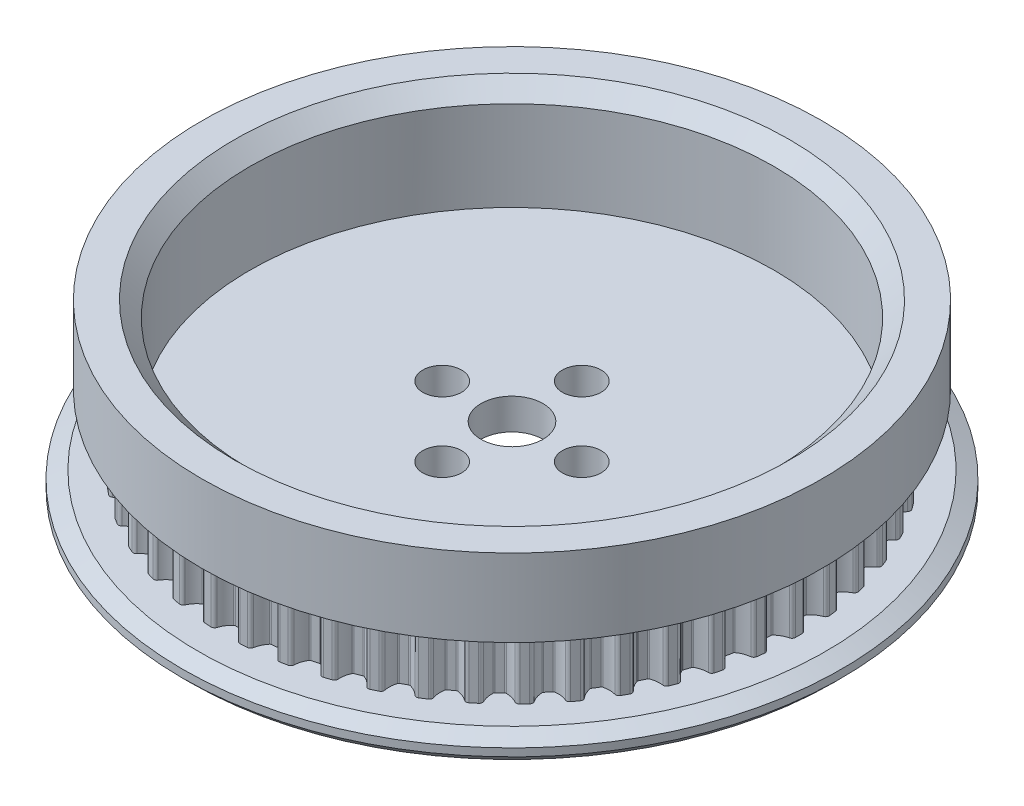
SolidWorks part; units mm, degrees
material "Markforged"
ref_plane "Front Plane" through (0, 0, 0) normal (0, 0, 1) x (1, 0, 0)
ref_plane "Top Plane" through (0, 0, 0) normal (0, 1, 0) x (1, 0, 0)
ref_plane "Right Plane" through (0, 0, 0) normal (1, 0, 0) x (0, 0, -1)
sketch "Sketch1" plane through (0, 0, 0) normal (0, 1, 0) x (1, 0, 0)
  line L0 (0, 0) -> (0, 22.38) construction
  arc B0 (21.7341, -8.9112) -> (21.9436, -8.382) centre (0, 0) ccw
  arc B1 (21.9436, -8.382) -> (21.8443, -8.0539) centre (21.682, -8.2821) ccw
  arc B2 (21.2042, -7.2904) -> (21.8443, -8.0539) centre (22.9888, -6.4443) ccw
  arc B3 (21.1977, -7.178) -> (21.2042, -7.2904) centre (21.3397, -7.2261) ccw
  arc B4 (21.1977, -7.178) -> (21.3684, -6.6526) centre (0, 0) ccw
  arc B5 (21.4397, -6.5655) -> (21.3684, -6.6526) centre (21.5116, -6.6971) ccw
  arc B6 (22.4064, -6.324) -> (21.4397, -6.5655) centre (22.3862, -8.2989) ccw
  arc B7 (22.4064, -6.324) -> (22.6796, -6.1169) centre (22.4092, -6.044) ccw
  arc B8 (22.6796, -6.1169) -> (22.8211, -5.5657) centre (0, 0) ccw
  arc B9 (22.8211, -5.5657) -> (22.6815, -5.2526) centre (22.5491, -5.4993) ccw
  arc B10 (21.9507, -4.5753) -> (22.6815, -5.2526) centre (23.6152, -3.5123) ccw
  arc B11 (21.9302, -4.4646) -> (21.9507, -4.5753) centre (22.0771, -4.4945) ccw
  arc B12 (21.9302, -4.4646) -> (22.0337, -3.9219) centre (0, 0) ccw
  arc B13 (22.0935, -3.8266) -> (22.0337, -3.9219) centre (22.1814, -3.9482) ccw
  arc B14 (23.0223, -3.4659) -> (22.0935, -3.8266) centre (23.2498, -5.4277) ccw
  arc B15 (23.0223, -3.4659) -> (23.2674, -3.2262) centre (22.99, -3.1877) ccw
  arc B16 (23.2674, -3.2262) -> (23.3387, -2.6615) centre (0, 0) ccw
  arc B17 (23.3387, -2.6615) -> (23.1609, -2.3684) centre (23.0605, -2.6298) ccw
  arc B18 (22.3511, -1.788) -> (23.1609, -2.3684) centre (23.8692, -0.5248) ccw
  arc B19 (22.3168, -1.6808) -> (22.3511, -1.788) centre (22.4664, -1.6921) ccw
  arc B20 (22.3168, -1.6808) -> (22.3515, -1.1295) centre (0, 0) ccw
  arc B21 (22.3989, -1.0274) -> (22.3515, -1.1295) centre (22.5013, -1.137) ccw
  arc B22 (23.2752, -0.5531) -> (22.3989, -1.0274) centre (23.7468, -2.4709) ccw
  arc B23 (23.2752, -0.5531) -> (23.4883, -0.2846) centre (23.2083, -0.2812) ccw
  arc B24 (23.4883, -0.2846) -> (23.4883, 0.2846) centre (0, 0) ccw
  arc B25 (23.4883, 0.2846) -> (23.2752, 0.5531) centre (23.2083, 0.2812) ccw
  arc B26 (22.3989, 1.0274) -> (23.2752, 0.5531) centre (23.7468, 2.4709) ccw
  arc B27 (22.3515, 1.1295) -> (22.3989, 1.0274) centre (22.5013, 1.137) ccw
  arc B28 (22.3515, 1.1295) -> (22.3168, 1.6808) centre (0, 0) ccw
  arc B29 (22.3511, 1.788) -> (22.3168, 1.6808) centre (22.4664, 1.6921) ccw
  arc B30 (23.1609, 2.3684) -> (22.3511, 1.788) centre (23.8692, 0.5248) ccw
  arc B31 (23.1609, 2.3684) -> (23.3387, 2.6615) centre (23.0605, 2.6298) ccw
  arc B32 (23.3387, 2.6615) -> (23.2674, 3.2262) centre (0, 0) ccw
  arc B33 (23.2674, 3.2262) -> (23.0223, 3.4659) centre (22.99, 3.1877) ccw
  arc B34 (22.0935, 3.8266) -> (23.0223, 3.4659) centre (23.2498, 5.4277) ccw
  arc B35 (22.0337, 3.9219) -> (22.0935, 3.8266) centre (22.1814, 3.9482) ccw
  arc B36 (22.0337, 3.9219) -> (21.9302, 4.4646) centre (0, 0) ccw
  arc B37 (21.9507, 4.5753) -> (21.9302, 4.4646) centre (22.0771, 4.4945) ccw
  arc B38 (22.6815, 5.2526) -> (21.9507, 4.5753) centre (23.6152, 3.5123) ccw
  arc B39 (22.6815, 5.2526) -> (22.8211, 5.5657) centre (22.5491, 5.4993) ccw
  arc B40 (22.8211, 5.5657) -> (22.6796, 6.1169) centre (0, 0) ccw
  arc B41 (22.6796, 6.1169) -> (22.4064, 6.324) centre (22.4092, 6.044) ccw
  arc B42 (21.4397, 6.5655) -> (22.4064, 6.324) centre (22.3862, 8.2989) ccw
  arc B43 (21.3684, 6.6526) -> (21.4397, 6.5655) centre (21.5116, 6.6971) ccw
  arc B44 (21.3684, 6.6526) -> (21.1977, 7.178) centre (0, 0) ccw
  arc B45 (21.2042, 7.2904) -> (21.1977, 7.178) centre (21.3397, 7.2261) ccw
  arc B46 (21.8443, 8.0539) -> (21.2042, 7.2904) centre (22.9888, 6.4443) ccw
  arc B47 (21.8443, 8.0539) -> (21.9436, 8.382) centre (21.682, 8.2821) ccw
  arc B48 (21.9436, 8.382) -> (21.7341, 8.9112) centre (0, 0) ccw
  arc B49 (21.7341, 8.9112) -> (21.4371, 9.0824) centre (21.475, 8.805) ccw
  arc B50 (20.4478, 9.2008) -> (21.4371, 9.0824) centre (21.1696, 11.0392) ccw
  arc B51 (20.3661, 9.2783) -> (20.4478, 9.2008) centre (20.5026, 9.3405) ccw
  arc B52 (20.3661, 9.2783) -> (20.1309, 9.7782) centre (0, 0) ccw
  arc B53 (20.1233, 9.8905) -> (20.1309, 9.7782) centre (20.2658, 9.8437) ccw
  arc B54 (20.6626, 10.7282) -> (20.1233, 9.8905) centre (21.9999, 9.2748) ccw
  arc B55 (20.6626, 10.7282) -> (20.72, 11.0662) centre (20.473, 10.9343) ccw
  arc B56 (20.72, 11.0662) -> (20.4458, 11.5649) centre (0, 0) ccw
  arc B57 (20.4458, 11.5649) -> (20.1297, 11.6976) centre (20.2021, 11.4271) ccw
  arc B58 (19.1334, 11.6911) -> (20.1297, 11.6976) centre (19.6191, 13.6054) ccw
  arc B59 (19.0426, 11.7577) -> (19.1334, 11.6911) centre (19.1703, 11.8365) ccw
  arc B60 (19.0426, 11.7577) -> (18.7466, 12.2241) centre (0, 0) ccw
  arc B61 (18.725, 12.3346) -> (18.7466, 12.2241) centre (18.8723, 12.3061) ccw
  arc B62 (19.1551, 13.2333) -> (18.725, 12.3346) centre (20.6639, 11.959) ccw
  arc B63 (19.1551, 13.2333) -> (19.1697, 13.5758) centre (18.9412, 13.414) ccw
  arc B64 (19.1697, 13.5758) -> (18.8351, 14.0363) centre (0, 0) ccw
  arc B65 (18.8351, 14.0363) -> (18.5049, 14.1283) centre (18.6106, 13.869) ccw
  arc B66 (17.5172, 13.9969) -> (18.5049, 14.1283) centre (17.7592, 15.9571) ccw
  arc B67 (17.4189, 14.0516) -> (17.5172, 13.9969) centre (17.5356, 14.1458) ccw
  arc B68 (17.4189, 14.0516) -> (17.0667, 14.4773) centre (0, 0) ccw
  arc B69 (17.0314, 14.5842) -> (17.0667, 14.4773) centre (17.1811, 14.5743) ccw
  arc B70 (17.3455, 15.5298) -> (17.0314, 14.5842) centre (19.0021, 14.4546) ccw
  arc B71 (17.3455, 15.5298) -> (17.317, 15.8714) centre (17.1106, 15.6822) ccw
  arc B72 (17.317, 15.8714) -> (16.9274, 16.2863) centre (0, 0) ccw
  arc B73 (16.9274, 16.2863) -> (16.5882, 16.3361) centre (16.7256, 16.0922) ccw
  arc B74 (15.6248, 16.082) -> (16.5882, 16.3361) centre (15.6192, 18.057) ccw
  arc B75 (15.5204, 16.124) -> (15.6248, 16.082) centre (15.6244, 16.232) ccw
  arc B76 (15.5204, 16.124) -> (15.1176, 16.5022) centre (0, 0) ccw
  arc B77 (15.0692, 16.6038) -> (15.1176, 16.5022) centre (15.219, 16.6128) ccw
  arc B78 (15.2623, 17.5813) -> (15.0692, 16.6038) centre (17.0407, 16.7222) ccw
  arc B79 (15.2623, 17.5813) -> (15.1913, 17.9166) centre (15.0102, 17.7031) ccw
  arc B80 (15.1913, 17.9166) -> (14.7527, 18.2794) centre (0, 0) ccw
  arc B81 (14.7527, 18.2794) -> (14.41, 18.2864) centre (14.5769, 18.0615) ccw
  arc B82 (13.486, 17.9135) -> (14.41, 18.2864) centre (13.2329, 19.8723) ccw
  arc B83 (13.3771, 17.9421) -> (13.486, 17.9135) centre (13.4668, 18.0623) ccw
  arc B84 (13.3771, 17.9421) -> (12.9302, 18.2668) centre (0, 0) ccw
  arc B85 (12.8694, 18.3615) -> (12.9302, 18.2668) centre (13.0168, 18.3892) ccw
  arc B86 (12.9384, 19.3555) -> (12.8694, 18.3615) centre (14.8105, 18.7261) ccw
  arc B87 (12.9384, 19.3555) -> (12.8259, 19.6793) centre (12.673, 19.4447) ccw
  arc B88 (12.8259, 19.6793) -> (12.3454, 19.9843) centre (0, 0) ccw
  arc B89 (12.3454, 19.9843) -> (12.0045, 19.9482) centre (12.1982, 19.7461) ccw
  arc B90 (11.1345, 19.4625) -> (12.0045, 19.9482) centre (10.6379, 21.3741) ccw
  arc B91 (11.0229, 19.4772) -> (11.1345, 19.4625) centre (11.0968, 19.6077) ccw
  arc B92 (11.0229, 19.4772) -> (10.5388, 19.7433) centre (0, 0) ccw
  arc B93 (10.4666, 19.8297) -> (10.5388, 19.7433) centre (10.6094, 19.8757) ccw
  arc B94 (10.4105, 20.8245) -> (10.4666, 19.8297) centre (12.3467, 20.4347) ccw
  arc B95 (10.4105, 20.8245) -> (10.2583, 21.1317) centre (10.136, 20.8798) ccw
  arc B96 (10.2583, 21.1317) -> (9.7433, 21.374) centre (0, 0) ccw
  arc B97 (9.7433, 21.374) -> (9.4096, 21.2955) centre (9.6272, 21.1192) ccw
  arc B98 (8.6074, 20.7046) -> (9.4096, 21.2955) centre (7.8751, 22.5388) ccw
  arc B99 (8.4948, 20.7051) -> (8.6074, 20.7046) centre (8.5518, 20.8439) ccw
  arc B100 (8.4948, 20.7051) -> (7.9812, 20.9085) centre (0, 0) ccw
  arc B101 (7.8987, 20.9852) -> (7.9812, 20.9085) centre (8.0347, 21.0486) ccw
  arc B102 (7.7184, 21.9651) -> (7.8987, 20.9852) centre (9.6882, 21.821) ccw
  arc B103 (7.7184, 21.9651) -> (7.5289, 22.2507) centre (7.4392, 21.9855) ccw
  arc B104 (7.5289, 22.2507) -> (6.9876, 22.4266) centre (0, 0) ccw
  arc B105 (6.9876, 22.4266) -> (6.6664, 22.3069) centre (6.9043, 22.1593) ccw
  arc B106 (5.9445, 21.6201) -> (6.6664, 22.3069) centre (4.9881, 23.3481) ccw
  arc B107 (5.8328, 21.6065) -> (5.9445, 21.6201) centre (5.8719, 21.7514) ccw
  arc B108 (5.8328, 21.6065) -> (5.2977, 21.7439) centre (0, 0) ccw
  arc B109 (5.2063, 21.8097) -> (5.2977, 21.7439) centre (5.3332, 21.8897) ccw
  arc B110 (4.9046, 22.7593) -> (5.2063, 21.8097) centre (6.8769, 22.8632) ccw
  arc B111 (4.9046, 22.7593) -> (4.6808, 23.0189) centre (4.625, 22.7445) ccw
  arc B112 (4.6808, 23.0189) -> (4.1217, 23.1256) centre (0, 0) ccw
  arc B113 (4.1217, 23.1256) -> (3.818, 22.9665) centre (4.0726, 22.8499) ccw
  arc B114 (3.188, 22.1947) -> (3.818, 22.9665) centre (2.0225, 23.7892) ccw
  arc B115 (3.0788, 22.1672) -> (3.188, 22.1947) centre (3.0994, 22.3158) ccw
  arc B116 (3.0788, 22.1672) -> (2.5307, 22.2365) centre (0, 0) ccw
  arc B117 (2.4318, 22.2902) -> (2.5307, 22.2365) centre (2.5476, 22.3855) ccw
  arc B118 (2.0135, 23.1945) -> (2.4318, 22.2902) centre (3.9571, 23.5448) ccw
  arc B119 (2.0135, 23.1945) -> (1.7589, 23.4241) centre (1.7379, 23.1448) ccw
  arc B120 (1.7589, 23.4241) -> (1.1908, 23.4598) centre (0, 0) ccw
  arc B121 (1.1908, 23.4598) -> (0.9095, 23.264) centre (1.1766, 23.1802) ccw
  arc B122 (0.3811, 22.4192) -> (0.9095, 23.264) centre (-0.975, 23.8551) ccw
  arc B123 (0.2762, 22.3783) -> (0.3811, 22.4192) centre (0.2781, 22.5283) ccw
  arc B124 (0.2762, 22.3783) -> (-0.2762, 22.3783) centre (0, 0) ccw
  arc B125 (-0.3811, 22.4192) -> (-0.2762, 22.3783) centre (-0.2781, 22.5283) ccw
  arc B126 (-0.9095, 23.264) -> (-0.3811, 22.4192) centre (0.975, 23.8551) ccw
  arc B127 (-0.9095, 23.264) -> (-1.1908, 23.4598) centre (-1.1766, 23.1802) ccw
  arc B128 (-1.1908, 23.4598) -> (-1.7589, 23.4241) centre (0, 0) ccw
  arc B129 (-1.7589, 23.4241) -> (-2.0135, 23.1945) centre (-1.7379, 23.1448) ccw
  arc B130 (-2.4318, 22.2902) -> (-2.0135, 23.1945) centre (-3.9571, 23.5448) ccw
  arc B131 (-2.5307, 22.2365) -> (-2.4318, 22.2902) centre (-2.5476, 22.3855) ccw
  arc B132 (-2.5307, 22.2365) -> (-3.0788, 22.1672) centre (0, 0) ccw
  arc B133 (-3.188, 22.1947) -> (-3.0788, 22.1672) centre (-3.0994, 22.3158) ccw
  arc B134 (-3.818, 22.9665) -> (-3.188, 22.1947) centre (-2.0225, 23.7892) ccw
  arc B135 (-3.818, 22.9665) -> (-4.1217, 23.1256) centre (-4.0726, 22.8499) ccw
  arc B136 (-4.1217, 23.1256) -> (-4.6808, 23.0189) centre (0, 0) ccw
  arc B137 (-4.6808, 23.0189) -> (-4.9046, 22.7593) centre (-4.625, 22.7445) ccw
  arc B138 (-5.2063, 21.8097) -> (-4.9046, 22.7593) centre (-6.8769, 22.8632) ccw
  arc B139 (-5.2977, 21.7439) -> (-5.2063, 21.8097) centre (-5.3332, 21.8897) ccw
  arc B140 (-5.2977, 21.7439) -> (-5.8328, 21.6065) centre (0, 0) ccw
  arc B141 (-5.9445, 21.6201) -> (-5.8328, 21.6065) centre (-5.8719, 21.7514) ccw
  arc B142 (-6.6664, 22.3069) -> (-5.9445, 21.6201) centre (-4.9881, 23.3481) ccw
  arc B143 (-6.6664, 22.3069) -> (-6.9876, 22.4266) centre (-6.9043, 22.1593) ccw
  arc B144 (-6.9876, 22.4266) -> (-7.5289, 22.2507) centre (0, 0) ccw
  arc B145 (-7.5289, 22.2507) -> (-7.7184, 21.9651) centre (-7.4392, 21.9855) ccw
  arc B146 (-7.8987, 20.9852) -> (-7.7184, 21.9651) centre (-9.6882, 21.821) ccw
  arc B147 (-7.9812, 20.9085) -> (-7.8987, 20.9852) centre (-8.0347, 21.0486) ccw
  arc B148 (-7.9812, 20.9085) -> (-8.4948, 20.7051) centre (0, 0) ccw
  arc B149 (-8.6074, 20.7046) -> (-8.4948, 20.7051) centre (-8.5518, 20.8439) ccw
  arc B150 (-9.4096, 21.2955) -> (-8.6074, 20.7046) centre (-7.8751, 22.5388) ccw
  arc B151 (-9.4096, 21.2955) -> (-9.7433, 21.374) centre (-9.6272, 21.1192) ccw
  arc B152 (-9.7433, 21.374) -> (-10.2583, 21.1317) centre (0, 0) ccw
  arc B153 (-10.2583, 21.1317) -> (-10.4105, 20.8245) centre (-10.136, 20.8798) ccw
  arc B154 (-10.4666, 19.8297) -> (-10.4105, 20.8245) centre (-12.3467, 20.4347) ccw
  arc B155 (-10.5388, 19.7433) -> (-10.4666, 19.8297) centre (-10.6094, 19.8757) ccw
  arc B156 (-10.5388, 19.7433) -> (-11.0229, 19.4772) centre (0, 0) ccw
  arc B157 (-11.1345, 19.4625) -> (-11.0229, 19.4772) centre (-11.0968, 19.6077) ccw
  arc B158 (-12.0045, 19.9482) -> (-11.1345, 19.4625) centre (-10.6379, 21.3741) ccw
  arc B159 (-12.0045, 19.9482) -> (-12.3454, 19.9843) centre (-12.1982, 19.7461) ccw
  arc B160 (-12.3454, 19.9843) -> (-12.8259, 19.6793) centre (0, 0) ccw
  arc B161 (-12.8259, 19.6793) -> (-12.9384, 19.3555) centre (-12.673, 19.4447) ccw
  arc B162 (-12.8694, 18.3615) -> (-12.9384, 19.3555) centre (-14.8105, 18.7261) ccw
  arc B163 (-12.9302, 18.2668) -> (-12.8694, 18.3615) centre (-13.0168, 18.3892) ccw
  arc B164 (-12.9302, 18.2668) -> (-13.3771, 17.9421) centre (0, 0) ccw
  arc B165 (-13.486, 17.9135) -> (-13.3771, 17.9421) centre (-13.4668, 18.0623) ccw
  arc B166 (-14.41, 18.2864) -> (-13.486, 17.9135) centre (-13.2329, 19.8723) ccw
  arc B167 (-14.41, 18.2864) -> (-14.7527, 18.2794) centre (-14.5769, 18.0615) ccw
  arc B168 (-14.7527, 18.2794) -> (-15.1913, 17.9166) centre (0, 0) ccw
  arc B169 (-15.1913, 17.9166) -> (-15.2623, 17.5813) centre (-15.0102, 17.7031) ccw
  arc B170 (-15.0692, 16.6038) -> (-15.2623, 17.5813) centre (-17.0407, 16.7222) ccw
  arc B171 (-15.1176, 16.5022) -> (-15.0692, 16.6038) centre (-15.219, 16.6128) ccw
  arc B172 (-15.1176, 16.5022) -> (-15.5204, 16.124) centre (0, 0) ccw
  arc B173 (-15.6248, 16.082) -> (-15.5204, 16.124) centre (-15.6244, 16.232) ccw
  arc B174 (-16.5882, 16.3361) -> (-15.6248, 16.082) centre (-15.6192, 18.057) ccw
  arc B175 (-16.5882, 16.3361) -> (-16.9274, 16.2863) centre (-16.7256, 16.0922) ccw
  arc B176 (-16.9274, 16.2863) -> (-17.317, 15.8714) centre (0, 0) ccw
  arc B177 (-17.317, 15.8714) -> (-17.3455, 15.5298) centre (-17.1106, 15.6822) ccw
  arc B178 (-17.0314, 14.5842) -> (-17.3455, 15.5298) centre (-19.0021, 14.4546) ccw
  arc B179 (-17.0667, 14.4773) -> (-17.0314, 14.5842) centre (-17.1811, 14.5743) ccw
  arc B180 (-17.0667, 14.4773) -> (-17.4189, 14.0516) centre (0, 0) ccw
  arc B181 (-17.5172, 13.9969) -> (-17.4189, 14.0516) centre (-17.5356, 14.1458) ccw
  arc B182 (-18.5049, 14.1283) -> (-17.5172, 13.9969) centre (-17.7592, 15.9571) ccw
  arc B183 (-18.5049, 14.1283) -> (-18.8351, 14.0363) centre (-18.6106, 13.869) ccw
  arc B184 (-18.8351, 14.0363) -> (-19.1697, 13.5758) centre (0, 0) ccw
  arc B185 (-19.1697, 13.5758) -> (-19.1551, 13.2333) centre (-18.9412, 13.414) ccw
  arc B186 (-18.725, 12.3346) -> (-19.1551, 13.2333) centre (-20.6639, 11.959) ccw
  arc B187 (-18.7466, 12.2241) -> (-18.725, 12.3346) centre (-18.8723, 12.3061) ccw
  arc B188 (-18.7466, 12.2241) -> (-19.0426, 11.7577) centre (0, 0) ccw
  arc B189 (-19.1334, 11.6911) -> (-19.0426, 11.7577) centre (-19.1703, 11.8365) ccw
  arc B190 (-20.1297, 11.6976) -> (-19.1334, 11.6911) centre (-19.6191, 13.6054) ccw
  arc B191 (-20.1297, 11.6976) -> (-20.4458, 11.5649) centre (-20.2021, 11.4271) ccw
  arc B192 (-20.4458, 11.5649) -> (-20.72, 11.0662) centre (0, 0) ccw
  arc B193 (-20.72, 11.0662) -> (-20.6626, 10.7282) centre (-20.473, 10.9343) ccw
  arc B194 (-20.1233, 9.8905) -> (-20.6626, 10.7282) centre (-21.9999, 9.2748) ccw
  arc B195 (-20.1309, 9.7782) -> (-20.1233, 9.8905) centre (-20.2658, 9.8437) ccw
  arc B196 (-20.1309, 9.7782) -> (-20.3661, 9.2783) centre (0, 0) ccw
  arc B197 (-20.4478, 9.2008) -> (-20.3661, 9.2783) centre (-20.5026, 9.3405) ccw
  arc B198 (-21.4371, 9.0824) -> (-20.4478, 9.2008) centre (-21.1696, 11.0392) ccw
  arc B199 (-21.4371, 9.0824) -> (-21.7341, 8.9112) centre (-21.475, 8.805) ccw
  arc B200 (-21.7341, 8.9112) -> (-21.9436, 8.382) centre (0, 0) ccw
  arc B201 (-21.9436, 8.382) -> (-21.8443, 8.0539) centre (-21.682, 8.2821) ccw
  arc B202 (-21.2042, 7.2904) -> (-21.8443, 8.0539) centre (-22.9888, 6.4443) ccw
  arc B203 (-21.1977, 7.178) -> (-21.2042, 7.2904) centre (-21.3397, 7.2261) ccw
  arc B204 (-21.1977, 7.178) -> (-21.3684, 6.6526) centre (0, 0) ccw
  arc B205 (-21.4397, 6.5655) -> (-21.3684, 6.6526) centre (-21.5116, 6.6971) ccw
  arc B206 (-22.4064, 6.324) -> (-21.4397, 6.5655) centre (-22.3862, 8.2989) ccw
  arc B207 (-22.4064, 6.324) -> (-22.6796, 6.1169) centre (-22.4092, 6.044) ccw
  arc B208 (-22.6796, 6.1169) -> (-22.8211, 5.5657) centre (0, 0) ccw
  arc B209 (-22.8211, 5.5657) -> (-22.6815, 5.2526) centre (-22.5491, 5.4993) ccw
  arc B210 (-21.9507, 4.5753) -> (-22.6815, 5.2526) centre (-23.6152, 3.5123) ccw
  arc B211 (-21.9302, 4.4646) -> (-21.9507, 4.5753) centre (-22.0771, 4.4945) ccw
  arc B212 (-21.9302, 4.4646) -> (-22.0337, 3.9219) centre (0, 0) ccw
  arc B213 (-22.0935, 3.8266) -> (-22.0337, 3.9219) centre (-22.1814, 3.9482) ccw
  arc B214 (-23.0223, 3.4659) -> (-22.0935, 3.8266) centre (-23.2498, 5.4277) ccw
  arc B215 (-23.0223, 3.4659) -> (-23.2674, 3.2262) centre (-22.99, 3.1877) ccw
  arc B216 (-23.2674, 3.2262) -> (-23.3387, 2.6615) centre (0, 0) ccw
  arc B217 (-23.3387, 2.6615) -> (-23.1609, 2.3684) centre (-23.0605, 2.6298) ccw
  arc B218 (-22.3511, 1.788) -> (-23.1609, 2.3684) centre (-23.8692, 0.5248) ccw
  arc B219 (-22.3168, 1.6808) -> (-22.3511, 1.788) centre (-22.4664, 1.6921) ccw
  arc B220 (-22.3168, 1.6808) -> (-22.3515, 1.1295) centre (0, 0) ccw
  arc B221 (-22.3989, 1.0274) -> (-22.3515, 1.1295) centre (-22.5013, 1.137) ccw
  arc B222 (-23.2752, 0.5531) -> (-22.3989, 1.0274) centre (-23.7468, 2.4709) ccw
  arc B223 (-23.2752, 0.5531) -> (-23.4883, 0.2846) centre (-23.2083, 0.2812) ccw
  arc B224 (-23.4883, 0.2846) -> (-23.4883, -0.2846) centre (0, 0) ccw
  arc B225 (-23.4883, -0.2846) -> (-23.2752, -0.5531) centre (-23.2083, -0.2812) ccw
  arc B226 (-22.3989, -1.0274) -> (-23.2752, -0.5531) centre (-23.7468, -2.4709) ccw
  arc B227 (-22.3515, -1.1295) -> (-22.3989, -1.0274) centre (-22.5013, -1.137) ccw
  arc B228 (-22.3515, -1.1295) -> (-22.3168, -1.6808) centre (0, 0) ccw
  arc B229 (-22.3511, -1.788) -> (-22.3168, -1.6808) centre (-22.4664, -1.6921) ccw
  arc B230 (-23.1609, -2.3684) -> (-22.3511, -1.788) centre (-23.8692, -0.5248) ccw
  arc B231 (-23.1609, -2.3684) -> (-23.3387, -2.6615) centre (-23.0605, -2.6298) ccw
  arc B232 (-23.3387, -2.6615) -> (-23.2674, -3.2262) centre (0, 0) ccw
  arc B233 (-23.2674, -3.2262) -> (-23.0223, -3.4659) centre (-22.99, -3.1877) ccw
  arc B234 (-22.0935, -3.8266) -> (-23.0223, -3.4659) centre (-23.2498, -5.4277) ccw
  arc B235 (-22.0337, -3.9219) -> (-22.0935, -3.8266) centre (-22.1814, -3.9482) ccw
  arc B236 (-22.0337, -3.9219) -> (-21.9302, -4.4646) centre (0, 0) ccw
  arc B237 (-21.9507, -4.5753) -> (-21.9302, -4.4646) centre (-22.0771, -4.4945) ccw
  arc B238 (-22.6815, -5.2526) -> (-21.9507, -4.5753) centre (-23.6152, -3.5123) ccw
  arc B239 (-22.6815, -5.2526) -> (-22.8211, -5.5657) centre (-22.5491, -5.4993) ccw
  arc B240 (-22.8211, -5.5657) -> (-22.6796, -6.1169) centre (0, 0) ccw
  arc B241 (-22.6796, -6.1169) -> (-22.4064, -6.324) centre (-22.4092, -6.044) ccw
  arc B242 (-21.4397, -6.5655) -> (-22.4064, -6.324) centre (-22.3862, -8.2989) ccw
  arc B243 (-21.3684, -6.6526) -> (-21.4397, -6.5655) centre (-21.5116, -6.6971) ccw
  arc B244 (-21.3684, -6.6526) -> (-21.1977, -7.178) centre (0, 0) ccw
  arc B245 (-21.2042, -7.2904) -> (-21.1977, -7.178) centre (-21.3397, -7.2261) ccw
  arc B246 (-21.8443, -8.0539) -> (-21.2042, -7.2904) centre (-22.9888, -6.4443) ccw
  arc B247 (-21.8443, -8.0539) -> (-21.9436, -8.382) centre (-21.682, -8.2821) ccw
  arc B248 (-21.9436, -8.382) -> (-21.7341, -8.9112) centre (0, 0) ccw
  arc B249 (-21.7341, -8.9112) -> (-21.4371, -9.0824) centre (-21.475, -8.805) ccw
  arc B250 (-20.4478, -9.2008) -> (-21.4371, -9.0824) centre (-21.1696, -11.0392) ccw
  arc B251 (-20.3661, -9.2783) -> (-20.4478, -9.2008) centre (-20.5026, -9.3405) ccw
  arc B252 (-20.3661, -9.2783) -> (-20.1309, -9.7782) centre (0, 0) ccw
  arc B253 (-20.1233, -9.8905) -> (-20.1309, -9.7782) centre (-20.2658, -9.8437) ccw
  arc B254 (-20.6626, -10.7282) -> (-20.1233, -9.8905) centre (-21.9999, -9.2748) ccw
  arc B255 (-20.6626, -10.7282) -> (-20.72, -11.0662) centre (-20.473, -10.9343) ccw
  arc B256 (-20.72, -11.0662) -> (-20.4458, -11.5649) centre (0, 0) ccw
  arc B257 (-20.4458, -11.5649) -> (-20.1297, -11.6976) centre (-20.2021, -11.4271) ccw
  arc B258 (-19.1334, -11.6911) -> (-20.1297, -11.6976) centre (-19.6191, -13.6054) ccw
  arc B259 (-19.0426, -11.7577) -> (-19.1334, -11.6911) centre (-19.1703, -11.8365) ccw
  arc B260 (-19.0426, -11.7577) -> (-18.7466, -12.2241) centre (0, 0) ccw
  arc B261 (-18.725, -12.3346) -> (-18.7466, -12.2241) centre (-18.8723, -12.3061) ccw
  arc B262 (-19.1551, -13.2333) -> (-18.725, -12.3346) centre (-20.6639, -11.959) ccw
  arc B263 (-19.1551, -13.2333) -> (-19.1697, -13.5758) centre (-18.9412, -13.414) ccw
  arc B264 (-19.1697, -13.5758) -> (-18.8351, -14.0363) centre (0, 0) ccw
  arc B265 (-18.8351, -14.0363) -> (-18.5049, -14.1283) centre (-18.6106, -13.869) ccw
  arc B266 (-17.5172, -13.9969) -> (-18.5049, -14.1283) centre (-17.7592, -15.9571) ccw
  arc B267 (-17.4189, -14.0516) -> (-17.5172, -13.9969) centre (-17.5356, -14.1458) ccw
  arc B268 (-17.4189, -14.0516) -> (-17.0667, -14.4773) centre (0, 0) ccw
  arc B269 (-17.0314, -14.5842) -> (-17.0667, -14.4773) centre (-17.1811, -14.5743) ccw
  arc B270 (-17.3455, -15.5298) -> (-17.0314, -14.5842) centre (-19.0021, -14.4546) ccw
  arc B271 (-17.3455, -15.5298) -> (-17.317, -15.8714) centre (-17.1106, -15.6822) ccw
  arc B272 (-17.317, -15.8714) -> (-16.9274, -16.2863) centre (0, 0) ccw
  arc B273 (-16.9274, -16.2863) -> (-16.5882, -16.3361) centre (-16.7256, -16.0922) ccw
  arc B274 (-15.6248, -16.082) -> (-16.5882, -16.3361) centre (-15.6192, -18.057) ccw
  arc B275 (-15.5204, -16.124) -> (-15.6248, -16.082) centre (-15.6244, -16.232) ccw
  arc B276 (-15.5204, -16.124) -> (-15.1176, -16.5022) centre (0, 0) ccw
  arc B277 (-15.0692, -16.6038) -> (-15.1176, -16.5022) centre (-15.219, -16.6128) ccw
  arc B278 (-15.2623, -17.5813) -> (-15.0692, -16.6038) centre (-17.0407, -16.7222) ccw
  arc B279 (-15.2623, -17.5813) -> (-15.1913, -17.9166) centre (-15.0102, -17.7031) ccw
  arc B280 (-15.1913, -17.9166) -> (-14.7527, -18.2794) centre (0, 0) ccw
  arc B281 (-14.7527, -18.2794) -> (-14.41, -18.2864) centre (-14.5769, -18.0615) ccw
  arc B282 (-13.486, -17.9135) -> (-14.41, -18.2864) centre (-13.2329, -19.8723) ccw
  arc B283 (-13.3771, -17.9421) -> (-13.486, -17.9135) centre (-13.4668, -18.0623) ccw
  arc B284 (-13.3771, -17.9421) -> (-12.9302, -18.2668) centre (0, 0) ccw
  arc B285 (-12.8694, -18.3615) -> (-12.9302, -18.2668) centre (-13.0168, -18.3892) ccw
  arc B286 (-12.9384, -19.3555) -> (-12.8694, -18.3615) centre (-14.8105, -18.7261) ccw
  arc B287 (-12.9384, -19.3555) -> (-12.8259, -19.6793) centre (-12.673, -19.4447) ccw
  arc B288 (-12.8259, -19.6793) -> (-12.3454, -19.9843) centre (0, 0) ccw
  arc B289 (-12.3454, -19.9843) -> (-12.0045, -19.9482) centre (-12.1982, -19.7461) ccw
  arc B290 (-11.1345, -19.4625) -> (-12.0045, -19.9482) centre (-10.6379, -21.3741) ccw
  arc B291 (-11.0229, -19.4772) -> (-11.1345, -19.4625) centre (-11.0968, -19.6077) ccw
  arc B292 (-11.0229, -19.4772) -> (-10.5388, -19.7433) centre (0, 0) ccw
  arc B293 (-10.4666, -19.8297) -> (-10.5388, -19.7433) centre (-10.6094, -19.8757) ccw
  arc B294 (-10.4105, -20.8245) -> (-10.4666, -19.8297) centre (-12.3467, -20.4347) ccw
  arc B295 (-10.4105, -20.8245) -> (-10.2583, -21.1317) centre (-10.136, -20.8798) ccw
  arc B296 (-10.2583, -21.1317) -> (-9.7433, -21.374) centre (0, 0) ccw
  arc B297 (-9.7433, -21.374) -> (-9.4096, -21.2955) centre (-9.6272, -21.1192) ccw
  arc B298 (-8.6074, -20.7046) -> (-9.4096, -21.2955) centre (-7.8751, -22.5388) ccw
  arc B299 (-8.4948, -20.7051) -> (-8.6074, -20.7046) centre (-8.5518, -20.8439) ccw
  arc B300 (-8.4948, -20.7051) -> (-7.9812, -20.9085) centre (0, 0) ccw
  arc B301 (-7.8987, -20.9852) -> (-7.9812, -20.9085) centre (-8.0347, -21.0486) ccw
  arc B302 (-7.7184, -21.9651) -> (-7.8987, -20.9852) centre (-9.6882, -21.821) ccw
  arc B303 (-7.7184, -21.9651) -> (-7.5289, -22.2507) centre (-7.4392, -21.9855) ccw
  arc B304 (-7.5289, -22.2507) -> (-6.9876, -22.4266) centre (0, 0) ccw
  arc B305 (-6.9876, -22.4266) -> (-6.6664, -22.3069) centre (-6.9043, -22.1593) ccw
  arc B306 (-5.9445, -21.6201) -> (-6.6664, -22.3069) centre (-4.9881, -23.3481) ccw
  arc B307 (-5.8328, -21.6065) -> (-5.9445, -21.6201) centre (-5.8719, -21.7514) ccw
  arc B308 (-5.8328, -21.6065) -> (-5.2977, -21.7439) centre (0, 0) ccw
  arc B309 (-5.2063, -21.8097) -> (-5.2977, -21.7439) centre (-5.3332, -21.8897) ccw
  arc B310 (-4.9046, -22.7593) -> (-5.2063, -21.8097) centre (-6.8769, -22.8632) ccw
  arc B311 (-4.9046, -22.7593) -> (-4.6808, -23.0189) centre (-4.625, -22.7445) ccw
  arc B312 (-4.6808, -23.0189) -> (-4.1217, -23.1256) centre (0, 0) ccw
  arc B313 (-4.1217, -23.1256) -> (-3.818, -22.9665) centre (-4.0726, -22.8499) ccw
  arc B314 (-3.188, -22.1947) -> (-3.818, -22.9665) centre (-2.0225, -23.7892) ccw
  arc B315 (-3.0788, -22.1672) -> (-3.188, -22.1947) centre (-3.0994, -22.3158) ccw
  arc B316 (-3.0788, -22.1672) -> (-2.5307, -22.2365) centre (0, 0) ccw
  arc B317 (-2.4318, -22.2902) -> (-2.5307, -22.2365) centre (-2.5476, -22.3855) ccw
  arc B318 (-2.0135, -23.1945) -> (-2.4318, -22.2902) centre (-3.9571, -23.5448) ccw
  arc B319 (-2.0135, -23.1945) -> (-1.7589, -23.4241) centre (-1.7379, -23.1448) ccw
  arc B320 (-1.7589, -23.4241) -> (-1.1908, -23.4598) centre (0, 0) ccw
  arc B321 (-1.1908, -23.4598) -> (-0.9095, -23.264) centre (-1.1766, -23.1802) ccw
  arc B322 (-0.3811, -22.4192) -> (-0.9095, -23.264) centre (0.975, -23.8551) ccw
  arc B323 (-0.2762, -22.3783) -> (-0.3811, -22.4192) centre (-0.2781, -22.5283) ccw
  arc B324 (-0.2762, -22.3783) -> (0.2762, -22.3783) centre (0, 0) ccw
  arc B325 (0.3811, -22.4192) -> (0.2762, -22.3783) centre (0.2781, -22.5283) ccw
  arc B326 (0.9095, -23.264) -> (0.3811, -22.4192) centre (-0.975, -23.8551) ccw
  arc B327 (0.9095, -23.264) -> (1.1908, -23.4598) centre (1.1766, -23.1802) ccw
  arc B328 (1.1908, -23.4598) -> (1.7589, -23.4241) centre (0, 0) ccw
  arc B329 (1.7589, -23.4241) -> (2.0135, -23.1945) centre (1.7379, -23.1448) ccw
  arc B330 (2.4318, -22.2902) -> (2.0135, -23.1945) centre (3.9571, -23.5448) ccw
  arc B331 (2.5307, -22.2365) -> (2.4318, -22.2902) centre (2.5476, -22.3855) ccw
  arc B332 (2.5307, -22.2365) -> (3.0788, -22.1672) centre (0, 0) ccw
  arc B333 (3.188, -22.1947) -> (3.0788, -22.1672) centre (3.0994, -22.3158) ccw
  arc B334 (3.818, -22.9665) -> (3.188, -22.1947) centre (2.0225, -23.7892) ccw
  arc B335 (3.818, -22.9665) -> (4.1217, -23.1256) centre (4.0726, -22.8499) ccw
  arc B336 (4.1217, -23.1256) -> (4.6808, -23.0189) centre (0, 0) ccw
  arc B337 (4.6808, -23.0189) -> (4.9046, -22.7593) centre (4.625, -22.7445) ccw
  arc B338 (5.2063, -21.8097) -> (4.9046, -22.7593) centre (6.8769, -22.8632) ccw
  arc B339 (5.2977, -21.7439) -> (5.2063, -21.8097) centre (5.3332, -21.8897) ccw
  arc B340 (5.2977, -21.7439) -> (5.8328, -21.6065) centre (0, 0) ccw
  arc B341 (5.9445, -21.6201) -> (5.8328, -21.6065) centre (5.8719, -21.7514) ccw
  arc B342 (6.6664, -22.3069) -> (5.9445, -21.6201) centre (4.9881, -23.3481) ccw
  arc B343 (6.6664, -22.3069) -> (6.9876, -22.4266) centre (6.9043, -22.1593) ccw
  arc B344 (6.9876, -22.4266) -> (7.5289, -22.2507) centre (0, 0) ccw
  arc B345 (7.5289, -22.2507) -> (7.7184, -21.9651) centre (7.4392, -21.9855) ccw
  arc B346 (7.8987, -20.9852) -> (7.7184, -21.9651) centre (9.6882, -21.821) ccw
  arc B347 (7.9812, -20.9085) -> (7.8987, -20.9852) centre (8.0347, -21.0486) ccw
  arc B348 (7.9812, -20.9085) -> (8.4948, -20.7051) centre (0, 0) ccw
  arc B349 (8.6074, -20.7046) -> (8.4948, -20.7051) centre (8.5518, -20.8439) ccw
  arc B350 (9.4096, -21.2955) -> (8.6074, -20.7046) centre (7.8751, -22.5388) ccw
  arc B351 (9.4096, -21.2955) -> (9.7433, -21.374) centre (9.6272, -21.1192) ccw
  arc B352 (9.7433, -21.374) -> (10.2583, -21.1317) centre (0, 0) ccw
  arc B353 (10.2583, -21.1317) -> (10.4105, -20.8245) centre (10.136, -20.8798) ccw
  arc B354 (10.4666, -19.8297) -> (10.4105, -20.8245) centre (12.3467, -20.4347) ccw
  arc B355 (10.5388, -19.7433) -> (10.4666, -19.8297) centre (10.6094, -19.8757) ccw
  arc B356 (10.5388, -19.7433) -> (11.0229, -19.4772) centre (0, 0) ccw
  arc B357 (11.1345, -19.4625) -> (11.0229, -19.4772) centre (11.0968, -19.6077) ccw
  arc B358 (12.0045, -19.9482) -> (11.1345, -19.4625) centre (10.6379, -21.3741) ccw
  arc B359 (12.0045, -19.9482) -> (12.3454, -19.9843) centre (12.1982, -19.7461) ccw
  arc B360 (12.3454, -19.9843) -> (12.8259, -19.6793) centre (0, 0) ccw
  arc B361 (12.8259, -19.6793) -> (12.9384, -19.3555) centre (12.673, -19.4447) ccw
  arc B362 (12.8694, -18.3615) -> (12.9384, -19.3555) centre (14.8105, -18.7261) ccw
  arc B363 (12.9302, -18.2668) -> (12.8694, -18.3615) centre (13.0168, -18.3892) ccw
  arc B364 (12.9302, -18.2668) -> (13.3771, -17.9421) centre (0, 0) ccw
  arc B365 (13.486, -17.9135) -> (13.3771, -17.9421) centre (13.4668, -18.0623) ccw
  arc B366 (14.41, -18.2864) -> (13.486, -17.9135) centre (13.2329, -19.8723) ccw
  arc B367 (14.41, -18.2864) -> (14.7527, -18.2794) centre (14.5769, -18.0615) ccw
  arc B368 (14.7527, -18.2794) -> (15.1913, -17.9166) centre (0, 0) ccw
  arc B369 (15.1913, -17.9166) -> (15.2623, -17.5813) centre (15.0102, -17.7031) ccw
  arc B370 (15.0692, -16.6038) -> (15.2623, -17.5813) centre (17.0407, -16.7222) ccw
  arc B371 (15.1176, -16.5022) -> (15.0692, -16.6038) centre (15.219, -16.6128) ccw
  arc B372 (15.1176, -16.5022) -> (15.5204, -16.124) centre (0, 0) ccw
  arc B373 (15.6248, -16.082) -> (15.5204, -16.124) centre (15.6244, -16.232) ccw
  arc B374 (16.5882, -16.3361) -> (15.6248, -16.082) centre (15.6192, -18.057) ccw
  arc B375 (16.5882, -16.3361) -> (16.9274, -16.2863) centre (16.7256, -16.0922) ccw
  arc B376 (16.9274, -16.2863) -> (17.317, -15.8714) centre (0, 0) ccw
  arc B377 (17.317, -15.8714) -> (17.3455, -15.5298) centre (17.1106, -15.6822) ccw
  arc B378 (17.0314, -14.5842) -> (17.3455, -15.5298) centre (19.0021, -14.4546) ccw
  arc B379 (17.0667, -14.4773) -> (17.0314, -14.5842) centre (17.1811, -14.5743) ccw
  arc B380 (17.0667, -14.4773) -> (17.4189, -14.0516) centre (0, 0) ccw
  arc B381 (17.5172, -13.9969) -> (17.4189, -14.0516) centre (17.5356, -14.1458) ccw
  arc B382 (18.5049, -14.1283) -> (17.5172, -13.9969) centre (17.7592, -15.9571) ccw
  arc B383 (18.5049, -14.1283) -> (18.8351, -14.0363) centre (18.6106, -13.869) ccw
  arc B384 (18.8351, -14.0363) -> (19.1697, -13.5758) centre (0, 0) ccw
  arc B385 (19.1697, -13.5758) -> (19.1551, -13.2333) centre (18.9412, -13.414) ccw
  arc B386 (18.725, -12.3346) -> (19.1551, -13.2333) centre (20.6639, -11.959) ccw
  arc B387 (18.7466, -12.2241) -> (18.725, -12.3346) centre (18.8723, -12.3061) ccw
  arc B388 (18.7466, -12.2241) -> (19.0426, -11.7577) centre (0, 0) ccw
  arc B389 (19.1334, -11.6911) -> (19.0426, -11.7577) centre (19.1703, -11.8365) ccw
  arc B390 (20.1297, -11.6976) -> (19.1334, -11.6911) centre (19.6191, -13.6054) ccw
  arc B391 (20.1297, -11.6976) -> (20.4458, -11.5649) centre (20.2021, -11.4271) ccw
  arc B392 (20.4458, -11.5649) -> (20.72, -11.0662) centre (0, 0) ccw
  arc B393 (20.72, -11.0662) -> (20.6626, -10.7282) centre (20.473, -10.9343) ccw
  arc B394 (20.1233, -9.8905) -> (20.6626, -10.7282) centre (21.9999, -9.2748) ccw
  arc B395 (20.1309, -9.7782) -> (20.1233, -9.8905) centre (20.2658, -9.8437) ccw
  arc B396 (20.1309, -9.7782) -> (20.3661, -9.2783) centre (0, 0) ccw
  arc B397 (20.4478, -9.2008) -> (20.3661, -9.2783) centre (20.5026, -9.3405) ccw
  arc B398 (21.4371, -9.0824) -> (20.4478, -9.2008) centre (21.1696, -11.0392) ccw
  arc B399 (21.4371, -9.0824) -> (21.7341, -8.9112) centre (21.475, -8.805) ccw
sketch_block_instance "Block-50T s3m pully profile-1"
sketch_block "Block-50T s3m pully profile"
extrude "Boss-Extrude1" add sketch "Sketch1" along normal mid plane 5.08
sketch "Sketch2" plane through (0, 2.54, 0) normal (0, 1, 0) x (1, 0, 0)
  circle A0 centre (0, 0) radius 25.4
  dimension "D1" = 50.8
extrude "Boss-Extrude2" add sketch "Sketch2" along normal offset from surface (0.635 mm away) 3.175 up to plane "Top Plane"
sketch "Sketch3" plane through (0, -2.54, 0) normal (0, -1, 0) x (1, 0, 0)
  circle A0 centre (0, 0) radius 25.4 construction
  circle A1 centre (0, 0) radius 25.4
extrude "Boss-Extrude4" add sketch "Sketch3" along normal offset from surface (0.635 mm away) 6.35 up to face at (0, 3.175, 25.4)
sketch "Sketch4" plane through (0, -3.175, 0) normal (0, -1, 0) x (1, 0, 0)
  circle A0 centre (0, 0) radius 21.463
  circle A1 centre (0, 0) radius 21.336 construction
  dimension "D1" = 0.127
  dimension "D2" = 42.672
extrude "Cut-Extrude1" cut sketch "Sketch4" against normal through all
sketch "Sketch5" plane through (0, -3.175, 0) normal (0, -1, 0) x (1, 0, 0)
  circle A0 centre (0, 0) radius 21.463 construction
  circle A1 centre (0, 0) radius 21.463
  circle A2 centre (0, 0) radius 2.54
  dimension "D1" = 5.08
extrude "Boss-Extrude5" add sketch "Sketch5" against normal blind 4.0742
sketch "Sketch6" plane through (0, 3.175, 0) normal (0, 1, 0) x (1, 0, 0)
  circle A0 centre (0, 0) radius 25.4 construction
  circle A1 centre (0, 0) radius 21.463 construction
  circle A2 centre (0, 0) radius 25.4
  circle A3 centre (0, 0) radius 21.463
extrude "Boss-Extrude6" add sketch "Sketch6" along normal blind 6.35
sketch "Sketch7" plane through (0, -2.54, 0) normal (0, 1, 0) x (1, 0, 0)
  circle A2 centre (0, 0) radius 26.9875
  dimension "D1" = 53.975
extrude "Boss-Extrude7" add sketch "Sketch7" against normal blind 1.905
chamfer "Chamfer1" distance 1.27 distance2 0.635 1 edges at (0, 2.54, 25.4) first distance on face at (0, 2.54, 25.4)
chamfer "Chamfer2" distance 0.635 distance2 1.27 1 edges at (0, -2.54, 26.9875) first distance on face at (0, -4.445, 26.9875)
chamfer "Chamfer4" distance 1.27 angle 45 1 edges at (0, 9.525, 21.463)
sketch "Sketch8" plane through (0, 0, 0) normal (0, 0, 1) x (1, 0, 0)
  line L0 (21.463, 0.8992) -> (-21.463, 0.8992) construction
  line L1 (21.463, 0.8992) -> (-21.463, 0.8992) construction
  line L2 (-26.9875, -4.445) -> (26.9875, -4.445) construction
  line L3 (0, -1.6408) -> (-19.05, -1.6408)
  line L4 (0, -1.6408) -> (0, -4.445)
  line L5 (0, -4.445) -> (-19.05, -4.445)
  line L6 (-19.05, -1.6408) -> (-19.05, -4.445) construction
  line L7 (0, -1.6408) -> (-19.05, -4.445) construction
  line L8 (0, -4.445) -> (-19.05, -1.6408) construction
  line L10 (-19.05, -1.6408) -> (-21.59, -4.445)
  line L11 (-21.59, -4.445) -> (-19.05, -4.445)
  point P2 (-9.525, -3.0429)
  dimension "D1" = 2.54
  dimension "D2" = 2.54
  dimension "D3" = 19.05
revolve "Cut-Revolve1" cut sketch "Sketch8" angle 360 about L4
chamfer "Chamfer5" distance 0.635 angle 45 1 edges at (0, -4.445, 26.9875)
sketch "Sketch9" plane through (0, -1.6408, 0) normal (0, -1, 0) x (1, 0, 0)
  line L0 (0, 0) -> (0, 5.715) construction
  circle A0 centre (0, 5.715) radius 1.5875
  dimension "D2" = 3.175
  dimension "D1" = 5.715
extrude "Cut-Extrude2" cut sketch "Sketch9" against normal through all
pattern_circular "CirPattern1" count 4 over 360 about axis through (0, 78.192, 0) along (0, -1, 0) of "Cut-Extrude2" reverse direction yes
